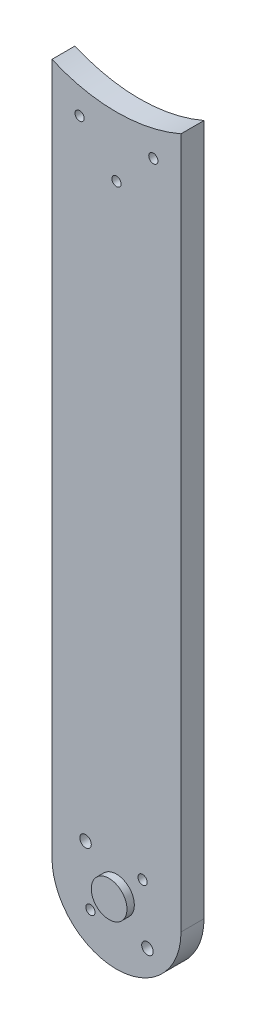
SolidWorks part; units mm, degrees
ref_plane "Front Plane" through (0, 0, 0) normal (0, 0, 1) x (1, 0, 0)
ref_plane "Top Plane" through (0, 0, 0) normal (0, 1, 0) x (1, 0, 0)
ref_plane "Right Plane" through (0, 0, 0) normal (1, 0, 0) x (0, 0, -1)
sketch "Sketch1" plane through (0, 0, 0) normal (0, 0, 1) x (1, 0, 0)
  line L0 (-14, 0) -> (-14, 150)
  line L1 (0, 147.078) -> (0, -14) construction
  line L2 (14, 0) -> (14, 150)
  line L3 (-14, 0) -> (14, 0) construction
  line L4 (-6.7175, 6.7175) -> (6.72, -6.72) construction
  line L5 (0, 0) -> (-8.9439, -8.9439) construction
  line L6 (-8.9439, -8.9439) -> (9.2803, 9.2803) construction
  arc A0 (-14, 0) -> (14, 0) centre (0, 0) ccw
  arc A1 (-14, 150) -> (14, 150) centre (0, 182.078) ccw
  circle A2 centre (-8, 142.376) radius 1
  circle A3 centre (6.72, -6.72) radius 1.25
  circle A4 centre (-5.6569, -5.6569) radius 1
  circle A5 centre (5.6569, 5.6569) radius 1
  circle A6 centre (-6.7175, 6.7175) radius 1.25
  circle A7 centre (8, 142.376) radius 1
  circle A8 centre (0, 134.0729) radius 1
  dimension "D1" = 2.5
  dimension "D3" = 14
  dimension "D5" = 2
  dimension "D2" = 2
  dimension "D4" = 16
  dimension "D8" = 35
  dimension "D10" = 45
  dimension "D11" = 2
  dimension "D6" = 40.5
  dimension "D7" = 11.53
  dimension "D9" = 9.5
  dimension "D12" = 8
  dimension "D14" = 9.5035
extrude "Boss-Extrude1" add sketch "Sketch1" along normal blind 5
sketch "Sketch2" plane through (0, 0, 5) normal (0, 0, 1) x (1, 0, 0)
  circle A0 centre (0, 0) radius 3.875
extrude "Boss-Extrude2" add sketch "Sketch2" along normal blind 1.6
